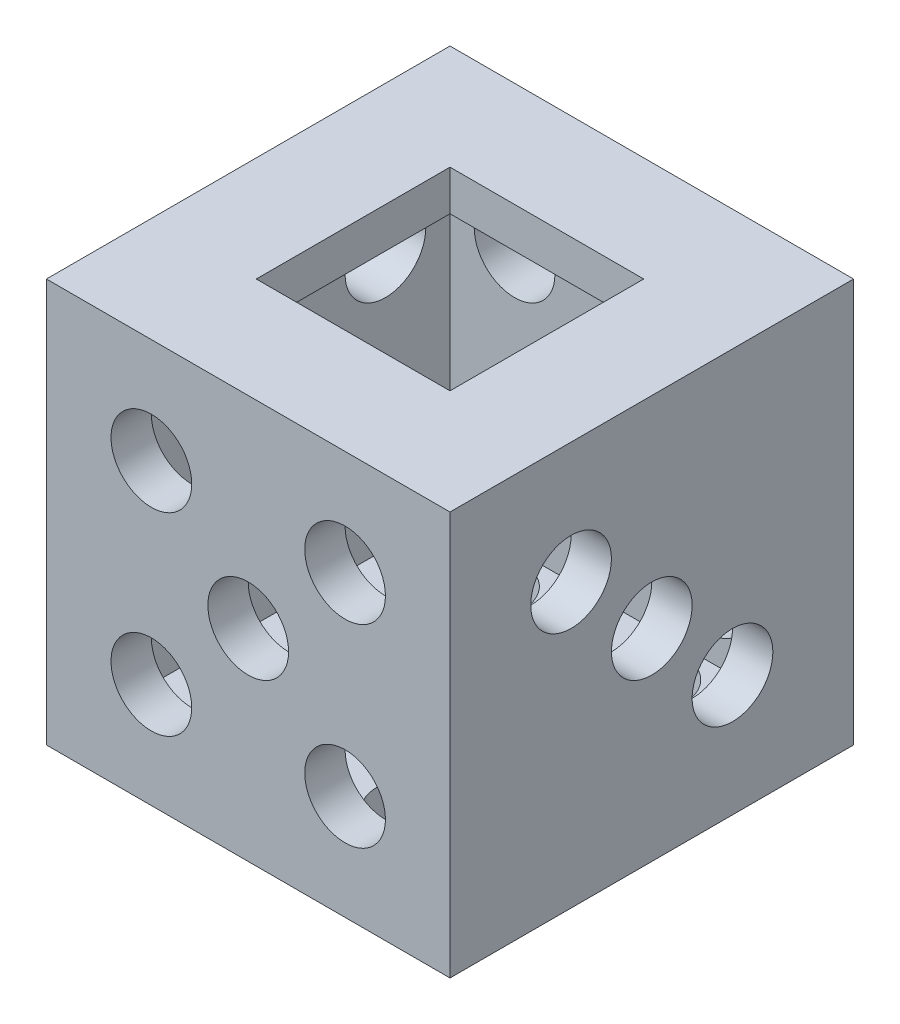
SolidWorks part; units mm, degrees
ref_plane "Front Plane" through (0, 0, 0) normal (0, 0, 1) x (1, 0, 0)
ref_plane "Top Plane" through (0, 0, 0) normal (0, 1, 0) x (1, 0, 0)
ref_plane "Right Plane" through (0, 0, 0) normal (1, 0, 0) x (0, 0, -1)
sketch "Sketch1" plane through (0, 0, 0) normal (0, 1, 0) x (1, 0, 0)
  line L1 (-12.5, 12.5) -> (12.5, 12.5)
  line L2 (-12.5, 12.5) -> (-12.5, -12.5)
  line L3 (-12.5, -12.5) -> (12.5, -12.5)
  line L4 (12.5, 12.5) -> (12.5, -12.5)
  line L5 (0, -12.5) -> (0, 12.5) construction
  line L6 (-12.5, 0) -> (12.5, 0) construction
  point P0 (0, 0)
  dimension "D1" = 25
  dimension "D2" = 25
extrude "Boss-Extrude1" add sketch "Sketch1" along normal blind 25
shell "Shell1" thickness 2.5
sketch "Sketch2" plane through (0, 25, 0) normal (0, 1, 0) x (1, 0, 0)
  line L1 (-6, 6) -> (6, 6)
  line L2 (-6, 6) -> (-6, -6)
  line L3 (-6, -6) -> (6, -6)
  line L4 (6, 6) -> (6, -6)
  line L5 (0, -6) -> (0, 6) construction
  line L6 (-6, 0) -> (6, 0) construction
  point P0 (0, 0)
  dimension "D1" = 12
  dimension "D2" = 12
extrude "Cut-Extrude1" cut sketch "Sketch2" against normal blind 15
sketch "Sketch3" plane through (0, 0, 0) normal (0, -1, 0) x (1, 0, 0)
  line L1 (10, 10) -> (-10, 10) construction
  line L2 (10, 10) -> (10, -10) construction
  line L3 (10, -10) -> (-10, -10) construction
  line L4 (-10, 10) -> (-10, -10) construction
  line L5 (0, -10) -> (0, 10) construction
  line L6 (10, 0) -> (-10, 0) construction
  line L7 (5, -7) -> (-5, -7) construction
  line L8 (5, -7) -> (5, 7) construction
  line L9 (5, 7) -> (-5, 7) construction
  line L10 (-5, -7) -> (-5, 7) construction
  line L11 (0, 7) -> (0, -7) construction
  line L12 (5, 0) -> (-5, 0) construction
  circle A0 centre (-5, 7) radius 2.5
  circle A1 centre (-5, 0) radius 2.5
  circle A2 centre (-5, -7) radius 2.5
  circle A3 centre (5, 7) radius 2.5
  circle A4 centre (5, 0) radius 2.5
  circle A5 centre (5, -7) radius 2.5
  point P0 (0, 0)
  point P4 (0, 0)
  dimension "D5" = 5
  dimension "D6" = 5
  dimension "D7" = 5
  dimension "D8" = 5
  dimension "D1" = 20
  dimension "D2" = 20
  dimension "D3" = 10
  dimension "D4" = 14
extrude "Cut-Extrude2" cut sketch "Sketch3" against normal blind 15
sketch "Sketch4" plane through (12.5, 0, 0) normal (1, 0, 0) x (0, 0, -1)
  line L4 (-12.5, 0) -> (12.5, 0)
  line L5 (12.5, 0) -> (12.5, 25)
  line L6 (12.5, 25) -> (-12.5, 25)
  line L7 (-12.5, 25) -> (-12.5, 0)
  line L8 (-12.5, 0) -> (12.5, 0)
  line L10 (12.5, 25) -> (-12.5, 25)
  line L11 (-12.5, 25) -> (-12.5, 0)
  circle A0 centre (-5, 17.5) radius 2.5
  circle A1 centre (0, 12.5) radius 2.5
  circle A2 centre (5, 7.5) radius 2.5
  dimension "D5" = 5
  dimension "D6" = 5
  dimension "D7" = 5
  dimension "D1" = 0
extrude "Cut-Extrude6" cut sketch "Sketch4" against normal blind 15 contours A0
extrude "Cut-Extrude7" cut sketch "Sketch4<3>" against normal blind 15 contours A1 | A2 region at (12.5, 12.5, 0) region at (12.5, 7.5, -5)
sketch "Sketch4<3>" plane through (12.5, 0, 0) normal (1, 0, 0) x (0, 0, -1) same geometry as "Sketch4"
sketch "Sketch5" plane through (-12.5, 0, 0) normal (-1, 0, 0) x (0, 0, 1)
  line L0 (-12.5, 12.5) -> (0, 12.5) construction
  line L2 (-10, 22.5) -> (10, 22.5) construction
  line L3 (-10, 22.5) -> (-10, 2.5) construction
  line L4 (-12.5, 0) -> (12.5, 0)
  line L5 (12.5, 0) -> (12.5, 25)
  line L6 (12.5, 25) -> (-12.5, 25)
  line L7 (-12.5, 25) -> (-12.5, 0)
  line L8 (-12.5, 0) -> (12.5, 0)
  line L9 (12.5, 0) -> (12.5, 25)
  line L10 (12.5, 25) -> (-12.5, 25)
  line L11 (-12.5, 25) -> (-12.5, 0)
  line L12 (-10, 2.5) -> (10, 2.5) construction
  line L13 (10, 22.5) -> (10, 2.5) construction
  line L14 (0, 2.5) -> (0, 22.5) construction
  line L15 (-10, 12.5) -> (10, 12.5) construction
  line L16 (-6, 18.5) -> (6, 18.5) construction
  line L17 (-6, 18.5) -> (-6, 6.5) construction
  line L18 (-6, 6.5) -> (6, 6.5) construction
  line L19 (6, 18.5) -> (6, 6.5) construction
  line L20 (0, 6.5) -> (0, 18.5) construction
  line L21 (-6, 12.5) -> (6, 12.5) construction
  circle A0 centre (-6, 18.5) radius 2.5
  circle A1 centre (6, 18.5) radius 2.5
  circle A2 centre (6, 6.5) radius 2.5
  circle A3 centre (-6, 6.5) radius 2.5
  dimension "D6" = 5
  dimension "D7" = 5
  dimension "D8" = 5
  dimension "D9" = 5
  dimension "D2" = 20
  dimension "D3" = 20
  dimension "D4" = 12
  dimension "D5" = 12
  dimension "D1" = 0
extrude "Cut-Extrude8" cut sketch "Sketch5" against normal blind 15 contours A0
extrude "Cut-Extrude9" cut sketch "Sketch5<4>" against normal blind 15 contours A1
sketch "Sketch5<4>" plane through (-12.5, 0, 0) normal (-1, 0, 0) x (0, 0, 1) same geometry as "Sketch5"
extrude "Cut-Extrude10" cut sketch "Sketch5<5>" against normal blind 15 contours A3 | A2
sketch "Sketch5<5>" plane through (-12.5, 0, 0) normal (-1, 0, 0) x (0, 0, 1) same geometry as "Sketch5"
sketch "Sketch7" plane through (0, 0, 12.5) normal (0, 0, 1) x (1, 0, 0)
  line L0 (0, 25) -> (0, 12.5) construction
  line L2 (-10, 22.5) -> (10, 22.5) construction
  line L3 (-10, 22.5) -> (-10, 2.5) construction
  line L4 (-12.5, 0) -> (12.5, 0)
  line L5 (12.5, 0) -> (12.5, 25)
  line L6 (12.5, 25) -> (-12.5, 25)
  line L7 (-12.5, 25) -> (-12.5, 0)
  line L8 (-12.5, 0) -> (12.5, 0)
  line L9 (12.5, 0) -> (12.5, 25)
  line L10 (12.5, 25) -> (-12.5, 25)
  line L11 (-12.5, 25) -> (-12.5, 0)
  line L12 (-10, 2.5) -> (10, 2.5) construction
  line L13 (10, 22.5) -> (10, 2.5) construction
  line L14 (0, 2.5) -> (0, 22.5) construction
  line L15 (-10, 12.5) -> (10, 12.5) construction
  line L16 (-6, 18.5) -> (6, 18.5) construction
  line L17 (-6, 18.5) -> (-6, 6.5) construction
  line L18 (-6, 6.5) -> (6, 6.5) construction
  line L19 (6, 18.5) -> (6, 6.5) construction
  line L20 (0, 6.5) -> (0, 18.5) construction
  line L21 (-6, 12.5) -> (6, 12.5) construction
  circle A0 centre (-6, 18.5) radius 2.5
  circle A1 centre (0, 12.5) radius 2.5
  circle A2 centre (6, 18.5) radius 2.5
  circle A3 centre (6, 6.5) radius 2.5
  circle A4 centre (-6, 6.5) radius 2.5
  dimension "D7" = 5
  dimension "D8" = 5
  dimension "D9" = 5
  dimension "D10" = 5
  dimension "D11" = 5
  dimension "D2" = 12.5
  dimension "D3" = 20
  dimension "D4" = 20
  dimension "D5" = 12
  dimension "D6" = 12
  dimension "D1" = 0
extrude "Cut-Extrude11" cut sketch "Sketch7" against normal blind 15 contours A1 | A2 | A0 | A4 | A3
sketch "Sketch8" plane through (0, 0, -12.5) normal (0, 0, -1) x (-1, 0, 0)
  line L0 (0, 0) -> (0, 12.5) construction
  line L1 (10, 22.5) -> (-10, 2.5) construction
  line L2 (-10, 22.5) -> (10, 22.5) construction
  line L3 (-10, 22.5) -> (-10, 2.5) construction
  line L4 (-12.5, 0) -> (12.5, 0)
  line L5 (12.5, 0) -> (12.5, 25)
  line L6 (12.5, 25) -> (-12.5, 25)
  line L7 (-12.5, 25) -> (-12.5, 0)
  line L8 (-12.5, 0) -> (12.5, 0)
  line L9 (12.5, 0) -> (12.5, 25)
  line L10 (12.5, 25) -> (-12.5, 25)
  line L11 (-12.5, 25) -> (-12.5, 0)
  line L12 (-10, 2.5) -> (10, 2.5) construction
  line L13 (10, 22.5) -> (10, 2.5) construction
  line L14 (0, 2.5) -> (0, 22.5) construction
  line L15 (-10, 12.5) -> (10, 12.5) construction
  line L17 (-6, 18.5) -> (6, 18.5) construction
  line L18 (-6, 18.5) -> (-6, 6.5) construction
  line L19 (-6, 6.5) -> (6, 6.5) construction
  line L20 (6, 18.5) -> (6, 6.5) construction
  line L21 (0, 6.5) -> (0, 18.5) construction
  line L22 (-6, 12.5) -> (6, 12.5) construction
  circle A0 centre (6, 18.5) radius 2.5
  circle A1 centre (-6, 6.5) radius 2.5
  dimension "D7" = 5
  dimension "D8" = 5
  dimension "D2" = 12.5
  dimension "D3" = 20
  dimension "D4" = 20
  dimension "D5" = 12
  dimension "D6" = 12
  dimension "D1" = 0
extrude "Cut-Extrude12" cut sketch "Sketch8" against normal blind 15 contours A1 | A0
